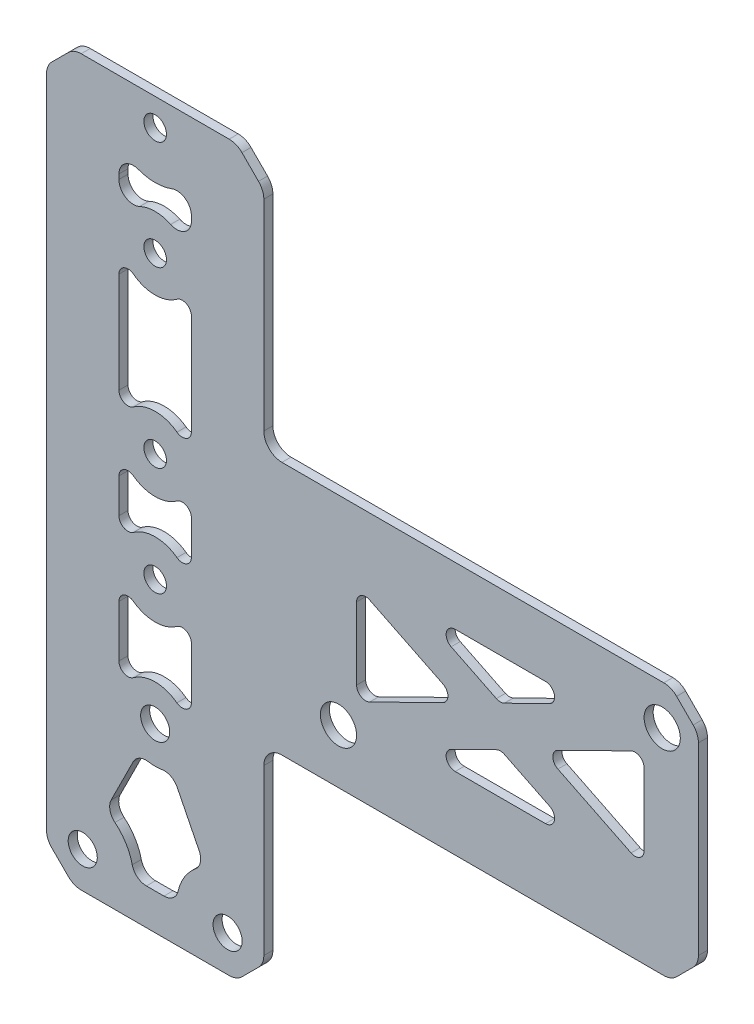
SolidWorks part; units mm, degrees
ref_plane "Front Plane" through (0, 0, 0) normal (0, 0, 1) x (1, 0, 0)
ref_plane "Top Plane" through (0, 0, 0) normal (0, 1, 0) x (1, 0, 0)
ref_plane "Right Plane" through (0, 0, 0) normal (1, 0, 0) x (0, 0, -1)
sketch "Sketch1" plane through (0, 0, 0) normal (0, 0, 1) x (1, 0, 0)
  line L1 (-19.05, 63.5) -> (19.05, 63.5)
  line L2 (-19.05, 63.5) -> (-19.05, -63.5)
  line L3 (-19.05, -63.5) -> (19.05, -63.5)
  line L4 (19.05, 63.5) -> (19.05, -63.5)
  line L5 (-19.05, 63.5) -> (19.05, -63.5) construction
  line L6 (-19.05, -63.5) -> (19.05, 63.5) construction
  line L7 (19.05, 19.05) -> (95.25, 19.05)
  line L8 (19.05, 19.05) -> (19.05, -25.4)
  line L9 (19.05, -25.4) -> (95.25, -25.4)
  line L10 (95.25, 19.05) -> (95.25, -25.4)
  circle A0 centre (32.1437, -15.875) radius 3.175
  circle A1 centre (88.9, 12.065) radius 3.175
  point P0 (0, 0)
  dimension "D7" = 6.35
  dimension "D1" = 44.45
  dimension "D2" = 38.1
  dimension "D3" = 76.2
  dimension "D4" = 127
  dimension "D5" = 6.35
  dimension "D6" = 47.625
  dimension "D8" = 27.94
  dimension "D9" = 56.7563
  dimension "D10" = 9.525
extrude "Boss-Extrude1" add sketch "Sketch1" along normal mid plane 1.5875 contours L10 L7 L4 L9 A1 A0 | L4 L1 L2 L3 region at (0, 0, 0) region at (57.0857, -3.1992, 0)
sketch "Sketch2" plane through (0, 0, 0.7937) normal (0, 0, 1) x (1, 0, 0)
  line L1 (-12.7, -57.15) -> (12.7, -57.15) construction
  line L2 (-19.05, -63.5) -> (19.05, -63.5) construction
  circle A0 centre (-12.7, -57.15) radius 2.5527
  circle A1 centre (12.7, -57.15) radius 2.5527
  circle A2 centre (0, -31.75) radius 2.5527
  circle A3 centre (0, -9.8425) radius 1.9812
  circle A4 centre (0, 9.2075) radius 1.9812
  circle A5 centre (0, 39.6875) radius 1.9812
  circle A6 centre (0, 58.7375) radius 1.9812
  point P14 (0, -57.15)
  dimension "D1" = 3.9624
  dimension "D2" = 5.1054
  dimension "D3" = 25.4
  dimension "D4" = 25.4
  dimension "D5" = 21.9075
  dimension "D6" = 6.35
  dimension "D7" = 19.05
  dimension "D8" = 30.48
  dimension "D9" = 19.05
extrude "Cut-Extrude1" cut sketch "Sketch2" against normal through all
sketch "Sketch3" plane through (0, 0, 0.7937) normal (0, 0, 1) x (1, 0, 0)
  line L0 (35.3187, -12.7) -> (85.725, -12.7)
  line L1 (32.1437, 12.065) -> (88.9, 12.065)
  line L2 (32.1437, 12.065) -> (32.1437, -15.875)
  line L3 (32.1437, -15.875) -> (88.9, -15.875)
  line L4 (88.9, 12.065) -> (88.9, -15.875)
  line L5 (32.1437, 12.065) -> (88.9, -15.875) construction
  line L6 (32.1437, -15.875) -> (88.9, 12.065) construction
  line L7 (85.725, 8.89) -> (85.725, -12.7)
  line L8 (35.3187, 8.89) -> (85.725, 8.89)
  line L9 (35.3187, 8.89) -> (35.3187, -12.7)
  line L10 (30.7414, 9.2165) -> (87.4977, -18.7235)
  line L11 (33.546, -18.7235) -> (90.3023, 9.2165)
  line L12 (33.546, 14.9135) -> (90.3023, -13.0265)
  line L13 (30.7414, -13.0265) -> (87.4977, 14.9135)
  circle A0 centre (32.1437, -15.875) radius 3.175 construction
  point P0 (60.5219, -1.905)
  dimension "D1" = 3.175
  dimension "D2" = 3.175
  dimension "D3" = 3.175
extrude "Cut-Extrude2" cut sketch "Sketch3" against normal through all contours L12 L13 L8 | L9 L13 L10 | L11 L0 L10 | L11 L12 L7 region at (60.5219, -10.2813, 0.7937) region at (41.3235, -1.905, 0.7937) region at (79.7202, -1.905, 0.7937) region at (60.5218, 6.4713, 0.7937)
fillet "Fillet2" radius 1.5875 12 edges at (60.5218, -5.4439, 0) (75.2617, -12.7, 0) (75.2617, 8.89, 0) (45.782, 8.89, 0) (60.5218, 1.6339, 0) (85.725, 6.9631, 0) (85.725, -10.7731, 0) (67.7106, -1.905, 0) (45.782, -12.7, 0) (53.3331, -1.905, 0) (35.3187, 6.9631, 0) (35.3187, -10.7731, 0)
chamfer "Chamfer1" distance 4.7625 angle 45 6 edges at (95.25, 19.05, 0) (95.25, -25.4, 0) (19.05, -63.5, 0) (-19.05, -63.5, 0) (19.05, 63.5, 0) (-19.05, 63.5, 0)
fillet "Fillet3" radius 3.175 14 edges at (95.25, -20.6375, 0) (90.4875, -25.4, 0) (19.05, -25.4, 0) (14.2875, -63.5, 0) (-14.2875, -63.5, 0) (-19.05, -58.7375, 0) (-19.05, 58.7375, 0) (-14.2875, 63.5, 0) (14.2875, 63.5, 0) (19.05, 58.7375, 0) (19.05, 19.05, 0) (90.4875, 19.05, 0) (95.25, 14.2875, 0) (19.05, -58.7375, 0)
sketch "Sketch5" plane through (0, 0, 0.7937) normal (0, 0, 1) x (1, 0, 0)
  line L28 (82.55, -12.7) -> (82.55, 6.35)
  line L29 (82.55, 6.35) -> (22.225, 6.35)
  line L30 (6.35, 22.225) -> (6.35, 50.8)
  line L31 (6.35, -31.75) -> (6.35, 50.8)
  line L32 (-6.35, 50.8) -> (-6.35, -50.8)
  line L33 (6.35, 50.8) -> (-6.35, 50.8)
  line L34 (6.35, 50.8) -> (-6.35, 50.8)
  line L35 (22.225, -12.7) -> (82.55, -12.7)
  line L36 (82.55, -12.7) -> (82.55, 6.35)
  line L37 (82.55, 6.35) -> (22.225, 6.35)
  line L38 (-6.35, -50.8) -> (6.35, -50.8)
  line L39 (-6.35, -50.8) -> (6.35, -50.8)
  line L40 (-6.35, 50.8) -> (-6.35, -50.8)
  line L41 (6.35, -50.8) -> (6.35, -28.575)
  line L42 (6.35, -50.8) -> (6.35, -31.75)
  line L43 (22.225, -12.7) -> (82.55, -12.7)
  circle A14 centre (0, 39.6875) radius 6.35
  circle A15 centre (0, 9.2075) radius 6.477
  circle A16 centre (0, -9.8425) radius 6.477
  circle A17 centre (0, -31.75) radius 6.35
  arc A28 (6.35, 22.225) -> (22.225, 6.35) centre (22.225, 22.225) ccw
  arc A29 (22.225, -12.7) -> (6.35, -28.575) centre (22.225, -28.575) ccw
  arc A30 (6.35, 22.225) -> (22.225, 6.35) centre (22.225, 22.225) ccw
  arc A31 (22.225, -12.7) -> (6.35, -28.575) centre (22.225, -28.575) ccw
  point P10 (0, 0)
  dimension "D2" = 12.7
  dimension "D3" = 12.7
  dimension "D4" = 12.954
  dimension "D1" = 12.7
extrude "Cut-Extrude3" cut sketch "Sketch5" against normal through all contours A17 L31 A16 L40 | A16 L31 A15 L40 | A15 L31 A14 L40 region at (0, -20.8989, 0.7937) region at (0, 24.5457, 0.7937) region at (0, -0.3175, 0.7937)
fillet "Fillet5" radius 1.5875 12 edges at (-6.35, -11.1188, 0) (6.35, -11.1188, 0) (6.35, -31.75, 0) (-6.35, -31.75, 0) (-6.35, 7.9312, 0) (6.35, 7.9312, 0) (6.35, -8.5662, 0) (-6.35, -8.5662, 0) (-6.35, 39.6875, 0) (6.35, 39.6875, 0) (6.35, 10.4838, 0) (-6.35, 10.4838, 0)
sketch "Sketch6" plane through (0, 0, 0.7937) normal (0, 0, 1) x (1, 0, 0)
  line L0 (0, -31.75) -> (-12.7, -57.15)
  line L1 (6.35, 31.6159) -> (-6.35, 31.6159)
  line L2 (6.35, 31.6159) -> (6.35, 61.6628)
  line L3 (6.35, 61.6628) -> (-6.35, 61.6628)
  line L4 (-6.35, 31.6159) -> (-6.35, 61.6628)
  line L5 (6.35, 31.6159) -> (-6.35, 61.6628) construction
  line L6 (6.35, 61.6628) -> (-6.35, 31.6159) construction
  line L7 (-12.7, -57.15) -> (12.7, -57.15)
  line L8 (12.7, -57.15) -> (0, -31.75)
  circle A0 centre (0, 39.6875) radius 6.35
  circle A1 centre (0, -31.75) radius 6.4738
  circle A2 centre (0, 58.7375) radius 8.3312
  circle A3 centre (0, 58.7375) radius 8.3312
  circle A5 centre (12.7, -57.15) radius 8.9027
  circle A6 centre (12.7, -57.15) radius 8.9027
  circle A8 centre (-12.7, -57.15) radius 8.9027
  circle A9 centre (-12.7, -57.15) radius 8.9027
  point P9 (0, 46.6393)
  dimension "D4" = 12.7
  dimension "D1" = 6.35
  dimension "D2" = 6.35
  dimension "D3" = 6.35
extrude "Cut-Extrude4" cut sketch "Sketch6" against normal blind 2.54 contours A3 L4 A0 L2 | A9 L7 A6 L8 A1 L0 region at (0, -47.5934, 0.7937) region at (0, 47.8918, 0.7937)
fillet "Fillet6" radius 2.54 10 edges at (3.7973, -57.15, 0) (8.7186, -49.1872, 0) (-3.7973, -57.15, 0) (-8.7186, -49.1872, 0) (-2.8952, -37.5404, 0) (2.8952, -37.5404, 0) (6.35, 39.6875, 0) (-6.35, 39.6875, 0) (6.35, 53.3443, 0) (-6.35, 53.3443, 0)
